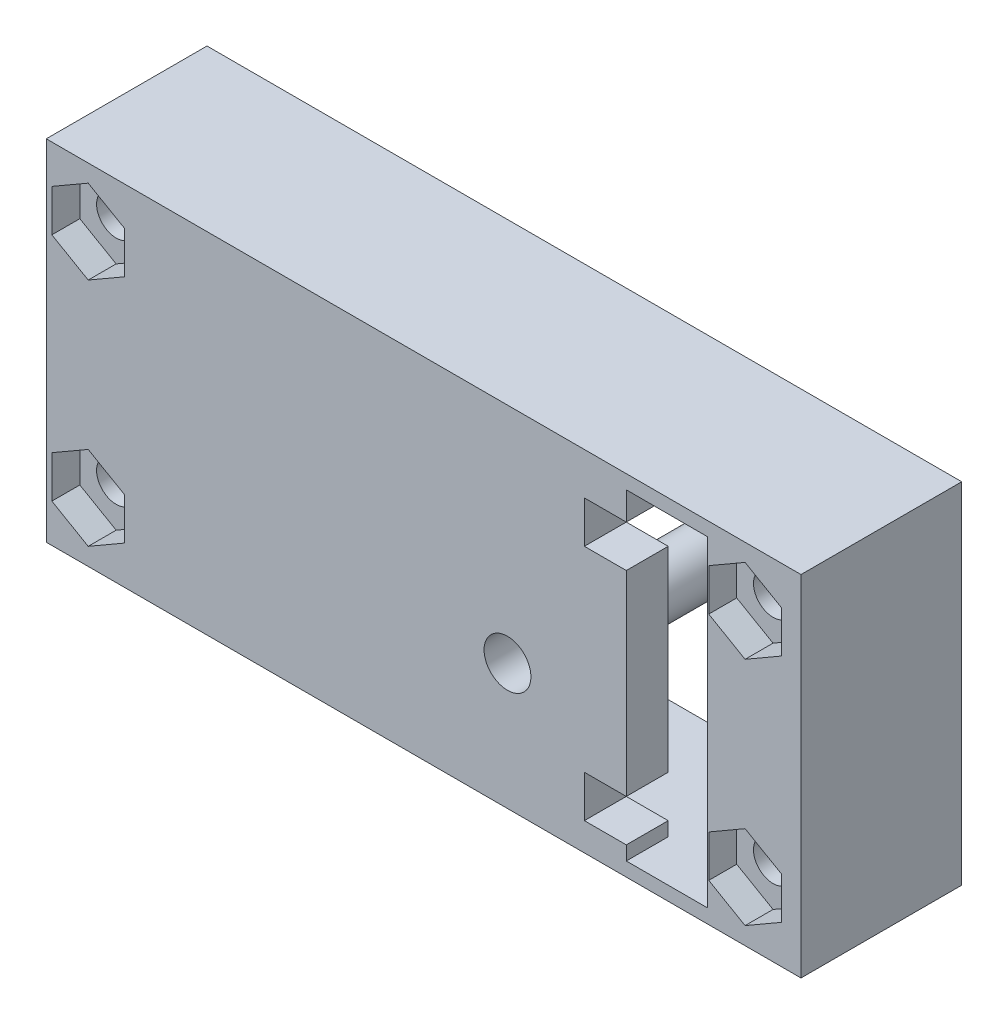
SolidWorks part; units mm, degrees
ref_plane "Front Plane" through (0, 0, 0) normal (0, 0, 1) x (1, 0, 0)
ref_plane "Top Plane" through (0, 0, 0) normal (0, 1, 0) x (1, 0, 0)
ref_plane "Right Plane" through (0, 0, 0) normal (1, 0, 0) x (0, 0, -1)
sketch "Sketch1" plane through (0, 0, 0) normal (0, 0, 1) x (1, 0, 0)
  line L1 (27, -12.5) -> (-27, -12.5)
  line L2 (27, -12.5) -> (27, 12.5)
  line L3 (27, 12.5) -> (-27, 12.5)
  line L4 (-27, -12.5) -> (-27, 12.5)
  line L5 (27, -12.5) -> (-27, 12.5) construction
  line L6 (27, 12.5) -> (-27, -12.5) construction
  line L7 (26, -11.5) -> (-26, -11.5)
  line L8 (26, -11.5) -> (26, 11.5)
  line L9 (26, 11.5) -> (-26, 11.5)
  line L10 (-26, -11.5) -> (-26, 11.5)
  line L11 (26, -11.5) -> (-26, 11.5) construction
  line L12 (26, 11.5) -> (-26, -11.5) construction
  point P0 (0, 0)
  point P6 (0, 0)
  dimension "D1" = 52
  dimension "D2" = 23
  dimension "D3" = 1
  dimension "D4" = 1
extrude "Boss-Extrude1" add sketch "Sketch1" along normal blind 8.5
sketch "Sketch2" plane through (0, 0, 8.5) normal (0, 0, 1) x (1, 0, 0)
  line L1 (27, -12.5) -> (-27, -12.5)
  line L2 (27, -12.5) -> (27, 12.5)
  line L3 (27, 12.5) -> (-27, 12.5)
  line L4 (-27, -12.5) -> (-27, 12.5)
  line L5 (27, -12.5) -> (-27, 12.5) construction
  line L6 (27, 12.5) -> (-27, -12.5) construction
  point P0 (0, 0)
extrude "Boss-Extrude2" add sketch "Sketch2" along normal blind 3
sketch "Sketch4" plane through (0, 0, 8.5) normal (0, 0, -1) x (-1, 0, 0)
  line L0 (26, -11.5) -> (-26, -11.5) construction
  line L1 (-20.3, 11.5) -> (-14.5, 11.5)
  line L2 (-20.3, 11.5) -> (-20.3, -11.5)
  line L3 (-20.3, -11.5) -> (-14.5, -11.5)
  line L4 (-14.5, 11.5) -> (-14.5, -11.5)
  line L5 (26, 11.5) -> (26, -11.5) construction
  line L6 (-26, 11.5) -> (26, 11.5) construction
  dimension "D1" = 5.8
  dimension "D2" = 40.5
extrude "Cut-Extrude1" cut sketch "Sketch4" against normal blind 3
sketch "Sketch5" plane through (0, 0, 8.5) normal (0, 0, -1) x (-1, 0, 0)
  circle A0 centre (-10, 0) radius 2
  dimension "D1" = 4
  dimension "D2" = 10
extrude "Boss-Extrude3" add sketch "Sketch5" along normal blind 9.7
fillet "Fillet1" radius 2 1 edges at (12, 0, 8.5)
sketch "Sketch6" plane through (0, 0, 8.5) normal (0, 0, -1) x (-1, 0, 0)
  line L0 (24, 8.25) -> (24, -8.25) construction
  line L1 (26, 11.5) -> (26, -11.5) construction
  line L2 (-23, 8.25) -> (-23, -8.25) construction
  line L3 (-26, -11.5) -> (-26, 11.5) construction
  line L4 (-27, -12.5) -> (-27, 12.5) construction
  circle A0 centre (24, 8.25) radius 1.4
  circle A1 centre (24, -8.25) radius 1.4
  circle A2 centre (-23, 8.25) radius 1.4
  circle A3 centre (-23, -8.25) radius 1.4
  point P4 (24, 0)
  point P6 (0, 0)
  point P17 (-23, 0)
  dimension "D2" = 2.8
  dimension "D3" = 2.8
  dimension "D4" = 2
  dimension "D5" = 16.5
  dimension "D6" = 4
  dimension "D1" = 16.5
extrude "Cut-Extrude2" cut sketch "Sketch6" against normal blind 10
sketch "Sketch8" plane through (0, 0, 11.5) normal (0, 0, 1) x (1, 0, 0)
  line L1 (-26.6, 9.7511) -> (-26.6, 6.7489)
  line L2 (-26.6, 6.7489) -> (-24, 5.2478)
  line L3 (-24, 5.2478) -> (-21.4, 6.7489)
  line L4 (-21.4, 6.7489) -> (-21.4, 9.7511)
  line L5 (-21.4, 9.7511) -> (-24, 11.2522)
  line L6 (-24, 11.2522) -> (-26.6, 9.7511)
  line L7 (-24, -5.2478) -> (-26.6, -6.7489)
  line L8 (-26.6, -6.7489) -> (-26.6, -9.7511)
  line L9 (-26.6, -9.7511) -> (-24, -11.2522)
  line L10 (-24, -11.2522) -> (-21.4, -9.7511)
  line L11 (-21.4, -9.7511) -> (-21.4, -6.7489)
  line L12 (-21.4, -6.7489) -> (-24, -5.2478)
  line L13 (23, 11.2522) -> (20.4, 9.7511)
  line L14 (-27, 12.5) -> (-27, -12.5) construction
  line L15 (20.4, 9.7511) -> (20.4, 6.7489)
  line L16 (20.4, 6.7489) -> (23, 5.2478)
  line L17 (23, 5.2478) -> (25.6, 6.7489)
  line L18 (25.6, 6.7489) -> (25.6, 9.7511)
  line L19 (25.6, 9.7511) -> (23, 11.2522)
  line L20 (23, -5.2478) -> (20.4, -6.7489)
  line L21 (20.4, -6.7489) -> (20.4, -9.7511)
  line L22 (20.4, -9.7511) -> (23, -11.2522)
  line L23 (23, -11.2522) -> (25.6, -9.7511)
  line L24 (25.6, -9.7511) -> (25.6, -6.7489)
  line L25 (25.6, -6.7489) -> (23, -5.2478)
  circle A0 centre (-24, 8.25) radius 2.6 construction
  circle A1 centre (-24, -8.25) radius 2.6 construction
  circle A2 centre (23, 8.25) radius 2.6 construction
  circle A3 centre (23, -8.25) radius 2.6 construction
  dimension "D2" = 5.2
extrude "Cut-Extrude3" cut sketch "Sketch8" against normal blind 2
sketch "Sketch10" plane through (0, 0, 8.5) normal (0, 0, -1) x (-1, 0, 0)
  line L1 (26, 11.5) -> (17.3098, 11.5)
  line L2 (26, 11.5) -> (26, 3.9581)
  line L3 (26, 3.9581) -> (17.3098, 3.9581)
  line L4 (17.3098, 11.5) -> (17.3098, 3.9581)
  line L5 (26, -11.5) -> (16.8129, -11.5)
  line L6 (26, -11.5) -> (26, -4.0462)
  line L7 (26, -4.0462) -> (16.8129, -4.0462)
  line L8 (16.8129, -11.5) -> (16.8129, -4.0462)
  line L9 (-26, 11.5) -> (-20.6838, 11.5)
  line L10 (-26, 11.5) -> (-26, 4.9094)
  line L11 (-26, 4.9094) -> (-20.6838, 4.9094)
  line L12 (-20.6838, 11.5) -> (-20.6838, 4.9094)
  line L13 (-26, -11.5) -> (-20.0802, -11.5)
  line L14 (-26, -11.5) -> (-26, -4.507)
  line L15 (-26, -4.507) -> (-20.0802, -4.507)
  line L16 (-20.0802, -11.5) -> (-20.0802, -4.507)
  circle A0 centre (24, 8.25) radius 1.4
  circle A1 centre (24, -8.25) radius 1.4
  circle A2 centre (24, -8.25) radius 2.4
  circle A3 centre (24, 8.25) radius 2.4
  circle A4 centre (24, 8.25) radius 1.4 construction
  circle A5 centre (-23, 8.25) radius 1.4
  circle A6 centre (-23, 8.25) radius 2.4
  circle A7 centre (-23, -8.25) radius 1.4
  circle A8 centre (-23, -8.25) radius 2.4
  circle M13 centre (24, 8.25) radius 1.4
  circle M14 centre (24, -8.25) radius 1.4
  dimension "D1" = 1
  dimension "D2" = 1
sketch "Sketch11" plane through (0, 0, 8.5) normal (0, 0, -1) x (-1, 0, 0)
  line L0 (-14.5, -11.5) -> (-14.5, 11.5) construction
  line L1 (-14.5, 9.5) -> (-11.5, 9.5)
  line L2 (-14.5, 9.5) -> (-14.5, 6.5)
  line L3 (-14.5, 6.5) -> (-11.5, 6.5)
  line L4 (-11.5, 9.5) -> (-11.5, 6.5)
  line L5 (-26, 11.5) -> (26, 11.5) construction
  line L6 (-14.5, -7.5) -> (-11.5, -7.5)
  line L7 (-14.5, -7.5) -> (-14.5, -10.5)
  line L8 (-14.5, -10.5) -> (-11.5, -10.5)
  line L9 (-11.5, -7.5) -> (-11.5, -10.5)
  line L10 (26, -11.5) -> (-14.5, -11.5) construction
  line L13 (27, -12.5) -> (-27, -12.5) construction
  circle A0 centre (-6, -3.5) radius 1.675
  dimension "D1" = 3.35
  dimension "D6" = 9
  dimension "D7" = 8.5
  dimension "D2" = 3
  dimension "D3" = 3
  dimension "D4" = 2
  dimension "D5" = 1
extrude "Cut-Extrude4" cut sketch "Sketch11" against normal blind 10
extrude "Boss-Extrude5" add sketch "Sketch10" along normal blind 10 contours L2 A3 M13 | L6 A2 M14 region at (-25.9349, 8.25, 8.5) region at (-21.6651, -8.25, 8.5)
extrude "Boss-Extrude6" add sketch "Sketch10<5>" along normal up to surface (8.5 mm away) contours L10 A6 A5 | L14 A8 A7 region at (20.7511, 8.25, 8.5) region at (25.3321, -8.25, 8.5) up to face at (0, 0, 0)
sketch "Sketch10<5>" plane through (0, 0, 8.5) normal (0, 0, -1) x (-1, 0, 0) same geometry as "Sketch10"
sketch "Sketch14" plane through (0, 0, 8.5) normal (0, 0, -1) x (-1, 0, 0)
  line L0 (-14.5, -7.5) -> (-14.5, 6.5) construction
  line L1 (-6, -0.2668) -> (-8.8, -1.8834)
  line L2 (-8.8, -1.8834) -> (-8.8, -5.1166)
  line L3 (-8.8, -5.1166) -> (-6, -6.7332)
  line L4 (-6, -6.7332) -> (-3.2, -5.1166)
  line L5 (-3.2, -5.1166) -> (-3.2, -1.8834)
  line L6 (-3.2, -1.8834) -> (-6, -0.2668)
  line L7 (-6, 0.8879) -> (-9.8, -1.3061)
  line L8 (-9.8, -1.3061) -> (-9.8, -5.6939)
  line L9 (-9.8, -5.6939) -> (-6, -7.8879)
  line L10 (-6, -7.8879) -> (-2.2, -5.6939)
  line L11 (-2.2, -5.6939) -> (-2.2, -1.3061)
  line L12 (-2.2, -1.3061) -> (-6, 0.8879)
  circle A0 centre (-6, -3.5) radius 2.8 construction
  circle A1 centre (-6, -3.5) radius 3.8 construction
  dimension "D1" = 5.6
  dimension "D2" = 1
extrude "Boss-Extrude8" add sketch "Sketch14" along normal blind 2.5
sketch "Sketch15" plane through (0, 0, 6) normal (0, 0, -1) x (-1, 0, 0)
  line L1 (-6, -0.2668) -> (-8.8, -1.8834)
  line L2 (-8.8, -1.8834) -> (-8.8, -5.1166)
  line L3 (-8.8, -5.1166) -> (-6, -6.7332)
  line L4 (-6, -6.7332) -> (-3.2, -5.1166)
  line L5 (-3.2, -5.1166) -> (-3.2, -1.8834)
  line L6 (-3.2, -1.8834) -> (-6, -0.2668)
  circle A0 centre (-6, -3.5) radius 2.8 construction
extrude "Cut-Extrude5" cut sketch "Sketch15" against normal up to surface (2.5 mm away) up to face at (5.9672, -3.3829, 8.5)
chamfer "Chamfer1" distance 1 angle 45 4 edges at (-21.6, -8.25, 8.5) (-21.6, 8.25, 8.5) (25.4, -8.25, 8.5) (25.4, 8.25, 8.5)
